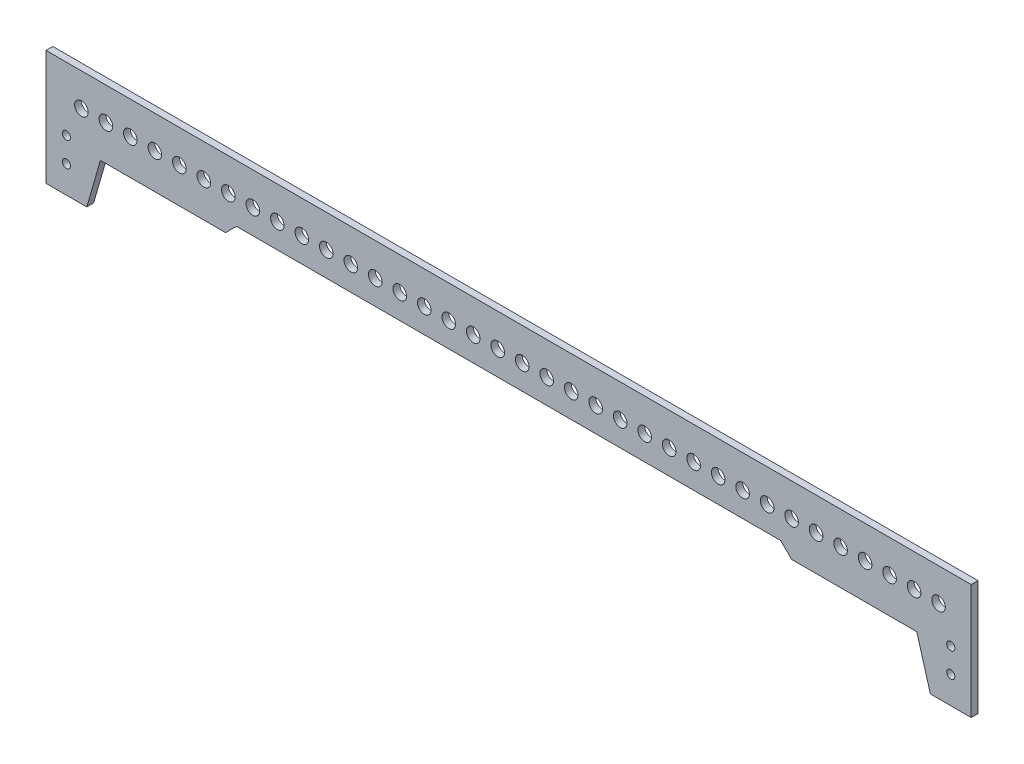
SolidWorks part; units mm, degrees
ref_plane "Front Plane" through (0, 0, 0) normal (0, 0, 1) x (1, 0, 0)
ref_plane "Top Plane" through (0, 0, 0) normal (0, 1, 0) x (1, 0, 0)
ref_plane "Right Plane" through (0, 0, 0) normal (1, 0, 0) x (0, 0, -1)
sketch "Sketch1" plane through (0, 0, 0) normal (0, 0, 1) x (1, 0, 0)
  line L0 (-215.9, 0) -> (215.9, 0)
  line L2 (215.9, -31.75) -> (132.08, -31.75)
  line L3 (132.08, -31.75) -> (127, -26.67)
  line L4 (127, -26.67) -> (-127, -26.67)
  line L5 (-127, -26.67) -> (-132.08, -31.75)
  line L6 (-132.08, -31.75) -> (-215.9, -31.75)
  line L8 (-215.9, -31.75) -> (-215.9, 0)
  line L9 (215.9, 0) -> (215.9, -31.75)
  dimension "D1" = 431.8
  dimension "D2" = 31.75
  dimension "D3" = 254
  dimension "D4" = 5.08
extrude "Boss-Extrude1" add sketch "Sketch1" along normal blind 3.175
sketch "Sketch3" plane through (0, 0, 3.175) normal (0, 0, 1) x (1, 0, 0)
  line L0 (215.9, 0) -> (-215.9, 0) construction
  line L2 (-199.39, -15.24) -> (-187.96, -15.24) construction
  line L3 (-215.9, 0) -> (-215.9, -31.75) construction
  circle A0 centre (-199.39, -15.24) radius 3.175
  circle A1 centre (-187.96, -15.24) radius 3.175
  circle A2 centre (-176.53, -15.24) radius 3.175
  circle A3 centre (-165.1, -15.24) radius 3.175
  circle A4 centre (-153.67, -15.24) radius 3.175
  circle A5 centre (-142.24, -15.24) radius 3.175
  circle A6 centre (-130.81, -15.24) radius 3.175
  circle A7 centre (-119.38, -15.24) radius 3.175
  circle A8 centre (-107.95, -15.24) radius 3.175
  circle A9 centre (-96.52, -15.24) radius 3.175
  circle A10 centre (-85.09, -15.24) radius 3.175
  circle A11 centre (-73.66, -15.24) radius 3.175
  circle A12 centre (-62.23, -15.24) radius 3.175
  circle A13 centre (-50.8, -15.24) radius 3.175
  circle A14 centre (-39.37, -15.24) radius 3.175
  circle A15 centre (-27.94, -15.24) radius 3.175
  circle A16 centre (-16.51, -15.24) radius 3.175
  circle A17 centre (-5.08, -15.24) radius 3.175
  circle A18 centre (6.35, -15.24) radius 3.175
  circle A19 centre (17.78, -15.24) radius 3.175
  circle A20 centre (29.21, -15.24) radius 3.175
  circle A21 centre (40.64, -15.24) radius 3.175
  circle A22 centre (52.07, -15.24) radius 3.175
  circle A23 centre (63.5, -15.24) radius 3.175
  circle A24 centre (74.93, -15.24) radius 3.175
  circle A25 centre (86.36, -15.24) radius 3.175
  circle A26 centre (97.79, -15.24) radius 3.175
  circle A27 centre (109.22, -15.24) radius 3.175
  circle A28 centre (120.65, -15.24) radius 3.175
  circle A29 centre (132.08, -15.24) radius 3.175
  circle A30 centre (143.51, -15.24) radius 3.175
  circle A31 centre (154.94, -15.24) radius 3.175
  circle A32 centre (166.37, -15.24) radius 3.175
  circle A33 centre (177.8, -15.24) radius 3.175
  circle A34 centre (189.23, -15.24) radius 3.175
  circle A35 centre (200.66, -15.24) radius 3.175
  dimension "D1" = 6.35
  dimension "D3" = 16.51
  dimension "D2" = 15.24
  dimension "D5" = 11.43
  dimension "D4" = 36
extrude "Cut-Extrude2" cut sketch "Sketch3" against normal through all
sketch "Sketch4" plane through (0, 0, 3.175) normal (0, 0, 1) x (1, 0, 0)
  line L0 (-215.9, -31.75) -> (-215.9, -53.75)
  line L1 (-215.9, -53.75) -> (-196.85, -53.75)
  line L2 (-196.85, -53.75) -> (-190.5, -31.75)
  line L3 (-215.9, -31.75) -> (-132.08, -31.75) construction
  line L4 (-190.5, -31.75) -> (-215.9, -31.75)
  line L5 (221.205, -53.75) -> (191.545, -53.75) construction
  point P9 (-185.5343, -31.75)
  point P10 (-197.3898, -53.75)
  point P11 (-190.434, -31.75)
  dimension "D1" = 25.4
  dimension "D2" = 19.05
extrude "Boss-Extrude2" add sketch "Sketch4" against normal up to surface (3.175 mm away) up to face at (-196.215, -15.24, 0)
sketch "Sketch5" plane through (0, 0, 3.175) normal (0, 0, 1) x (1, 0, 0)
  line L0 (-206.375, -53.75) -> (-206.375, 0) construction
  line L1 (-215.9, -53.75) -> (-196.85, -53.75) construction
  line L2 (215.9, 0) -> (-215.9, 0) construction
  circle A0 centre (-206.375, -41.05) radius 1.905
  circle A1 centre (-206.375, -29.62) radius 1.905
  point P8 (-203.1884, 0)
  point P11 (-203.4125, -56.7347)
  point P12 (-203.4125, -43.2217)
  point P13 (-203.4125, -31.8086)
  dimension "D3" = 3.81
  dimension "D1" = 12.7
  dimension "D2" = 11.43
extrude "Cut-Extrude3" cut sketch "Sketch5" against normal through all
mirror "Mirror1" about plane through (0, 0, 0) normal (1, 0, 0) of "Cut-Extrude3", "Boss-Extrude2"
